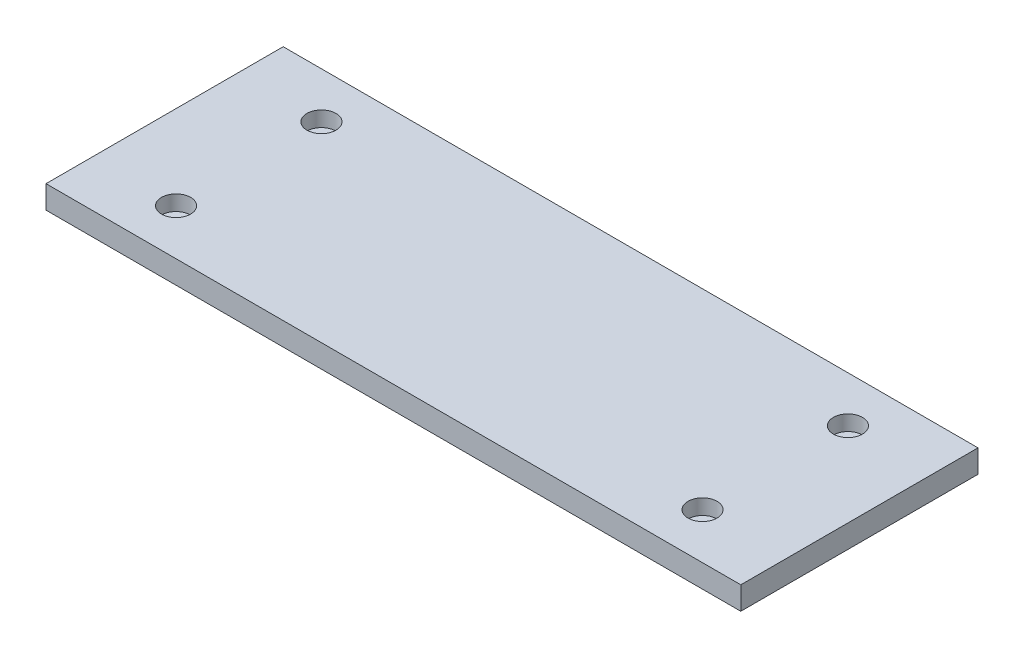
SolidWorks part; units mm, degrees
ref_plane "Front Plane" through (0, 0, 0) normal (0, 0, 1) x (1, 0, 0)
ref_plane "Top Plane" through (0, 0, 0) normal (0, 1, 0) x (1, 0, 0)
ref_plane "Right Plane" through (0, 0, 0) normal (1, 0, 0) x (0, 0, -1)
sketch "Sketch1" plane through (0, 0, 0) normal (0, 1, 0) x (1, 0, 0)
  line L0 (-45.4, 0) -> (45.4, 0) construction
  line L1 (-45.4, 15.5) -> (45.4, 15.5)
  line L2 (-45.4, 15.5) -> (-45.4, -15.5)
  line L3 (-45.4, -15.5) -> (45.4, -15.5)
  line L4 (45.4, 15.5) -> (45.4, -15.5)
  line L5 (0, 15.5) -> (0, -15.5) construction
  point P8 (0, 0)
  dimension "D1" = 90.8
  dimension "D2" = 31
extrude "Boss-Extrude1" add sketch "Sketch1" along normal blind 3
sketch "Sketch2" plane through (0, 3, 0) normal (0, 1, 0) x (1, 0, 0)
  line L0 (-34.4, 9.5) -> (-45.4, 9.5) construction
  line L1 (-45.4, 15.5) -> (-45.4, -15.5) construction
  line L2 (-34.4, -9.5) -> (-45.4, -9.5) construction
  line L3 (34.4, 9.5) -> (45.4, 9.5) construction
  line L4 (45.4, -15.5) -> (45.4, 15.5) construction
  line L5 (34.4, -9.5) -> (45.4, -9.5) construction
  line L6 (-34.4, 9.5) -> (-34.4, 15.5) construction
  line L7 (45.4, 15.5) -> (-45.4, 15.5) construction
  line L8 (34.4, 9.5) -> (34.4, 15.5) construction
  line L9 (34.4, -9.5) -> (34.4, -15.5) construction
  line L10 (-45.4, -15.5) -> (45.4, -15.5) construction
  line L11 (-34.4, -9.5) -> (-34.4, -15.5) construction
  circle A0 centre (-34.4, 9.5) radius 0.95
  circle A1 centre (34.4, 9.5) radius 0.95
  circle A2 centre (-34.4, -9.5) radius 0.95
  circle A3 centre (34.4, -9.5) radius 0.95
  dimension "D1" = 1.9
  dimension "D2" = 6
  dimension "D3" = 11
extrude "Cut-Extrude1" cut sketch "Sketch2" against normal blind 3
sketch "Sketch3" plane through (0, 3, 0) normal (0, 1, 0) x (1, 0, 0)
  circle A0 centre (-34.4, 9.5) radius 1.9
  circle A1 centre (-34.4, -9.5) radius 1.9
  circle A2 centre (34.4, 9.5) radius 1.9
  circle A3 centre (34.4, -9.5) radius 1.9
  dimension "D1" = 3.8
extrude "Cut-Extrude2" cut sketch "Sketch3" against normal blind 2
sketch "Sketch4" plane through (0, 0, 0) normal (0, -1, 0) x (1, 0, 0)
  line L0 (-27, 0) -> (27, 0) construction
  line L1 (-27, 3.5) -> (27, 3.5)
  line L2 (-27, 3.5) -> (-27, -3.5)
  line L3 (-27, -3.5) -> (27, -3.5)
  line L4 (27, 3.5) -> (27, -3.5)
  line L5 (0, 3.5) -> (0, -3.5) construction
  point P8 (0, 0)
  dimension "D1" = 54
  dimension "D2" = 7
extrude "Boss-Extrude2" add sketch "Sketch4" along normal blind 3
sketch "Sketch5" plane through (27, 0, 0) normal (1, 0, 0) x (0, 0, -1)
  line L0 (0, -3) -> (0, -4.1307) construction
  line L1 (3.5, -3) -> (-3.5, -3) construction
  circle A0 centre (0, -4.1307) radius 3.9
  dimension "D1" = 7.8
  dimension "D2" = 1.1307
extrude "Cut-Extrude3" cut sketch "Sketch5" against normal blind 54
